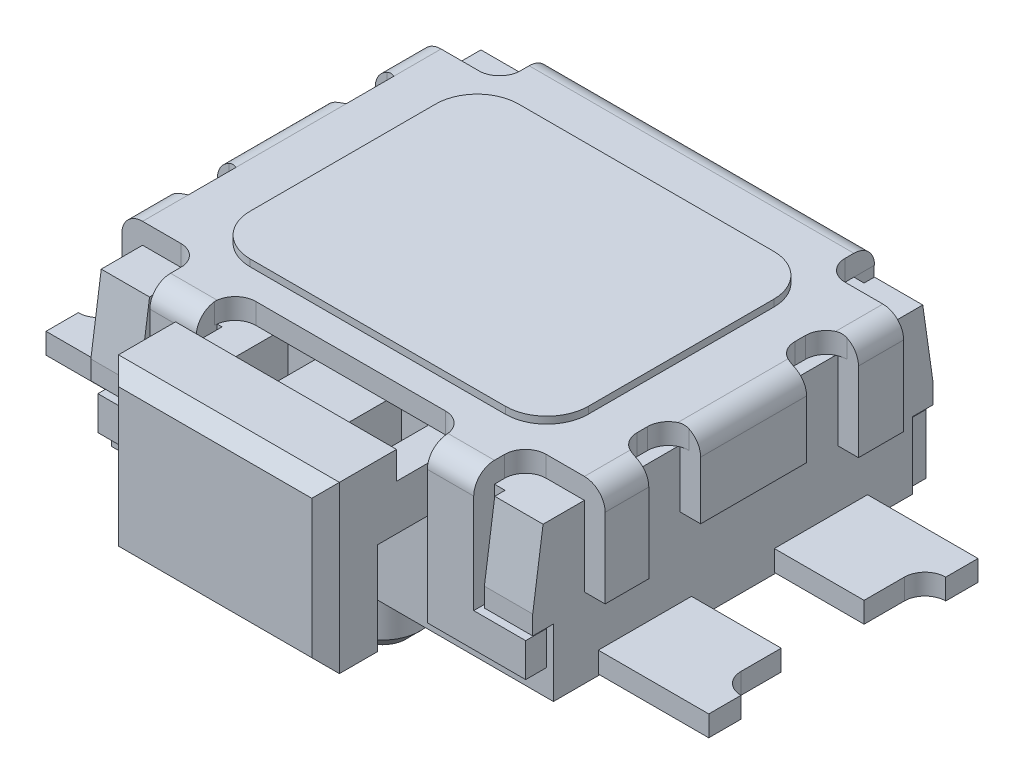
SolidWorks part; units mm, degrees
ref_plane "Front Plane" through (0, 0, 0) normal (0, 0, 1) x (1, 0, 0)
ref_plane "Top Plane" through (0, 0, 0) normal (0, 1, 0) x (1, 0, 0)
ref_plane "Right Plane" through (0, 0, 0) normal (1, 0, 0) x (0, 0, -1)
sketch "Sketch1" plane through (0, 0, 0) normal (0, 1, 0) x (1, 0, 0)
  line L1 (-1.75, 1.45) -> (1.75, 1.45)
  line L2 (-1.75, 1.45) -> (-1.75, -1.45)
  line L3 (-1.75, -1.45) -> (1.75, -1.45)
  line L4 (1.75, 1.45) -> (1.75, -1.45)
  line L5 (-1.75, 1.45) -> (1.75, -1.45) construction
  line L6 (-1.75, -1.45) -> (1.75, 1.45) construction
  point P0 (0, 0)
  dimension "D1" = 3.5
  dimension "D2" = 2.9
extrude "Boss-Extrude1" add sketch "Sketch1" along normal blind 1.3
fillet "Fillet1" radius 0.15 4 edges at (-1.75, 1.3, 0) (1.75, 1.3, 0) (0, 1.3, -1.45) (0, 1.3, 1.45)
sketch "Sketch2" plane through (0, 1.3, 0) normal (0, 1, 0) x (1, 0, 0)
  line L0 (4.873, 0.6414) -> (53.3412, 0.6414) construction
  line L1 (0, 1.45) -> (0, -1.3) construction
  line L2 (-1.75, 1.45) -> (-1.176, 1.45)
  line L3 (-1.75, 1.45) -> (-1.75, 1.0863)
  line L4 (-1.75, 1.0863) -> (-1.326, 1.0863)
  line L5 (-1.176, 1.45) -> (-1.176, 1.2363)
  line L6 (-1.75, 1.45) -> (1.75, 1.45) construction
  line L7 (-1.6, -1.3) -> (1.6, -1.3) construction
  line L8 (-1.75, -1.45) -> (-1.75, 1.45) construction
  line L9 (-1.75, -1.45) -> (-1.1728, -1.45)
  line L10 (-1.75, -1.45) -> (-1.75, -1.0755)
  line L11 (-1.75, -1.0755) -> (-1.3228, -1.0755)
  line L12 (-1.1728, -1.45) -> (-1.1728, -1.2255)
  line L13 (-1.75, 0.7594) -> (-1.6663, 0.7594)
  line L14 (-1.75, 0.7594) -> (-1.75, 0.3837)
  line L15 (-1.75, 0.3837) -> (-1.6663, 0.3837)
  line L16 (-1.5163, 0.6094) -> (-1.5163, 0.5337)
  line L17 (0, 0) -> (-1.75, 0) construction
  line L18 (-1.75, -0.3837) -> (-1.6663, -0.3837)
  line L19 (-1.5163, -0.6094) -> (-1.5163, -0.5337)
  line L20 (-1.75, -0.7594) -> (-1.6663, -0.7594)
  line L21 (-1.75, -0.7594) -> (-1.75, -0.3837)
  line L22 (1.75, -1.45) -> (-1.75, -1.45) construction
  line L23 (-0.8369, -1.45) -> (0.8369, -1.45)
  line L24 (-0.8369, -1.45) -> (-0.8369, -1.3181)
  line L25 (-0.6869, -1.1681) -> (0.6869, -1.1681)
  line L26 (0, -1.45) -> (0, -1.1681)
  line L27 (0.8369, -1.45) -> (0.8369, -1.3181)
  line L28 (1.75, -0.7594) -> (1.75, -0.3837)
  line L29 (1.75, -0.7594) -> (1.6663, -0.7594)
  line L30 (1.5163, -0.6094) -> (1.5163, -0.5337)
  line L31 (1.75, -0.3837) -> (1.6663, -0.3837)
  line L32 (1.75, 0.3837) -> (1.6663, 0.3837)
  line L33 (1.5163, 0.6094) -> (1.5163, 0.5337)
  line L34 (1.75, 0.7594) -> (1.6663, 0.7594)
  line L35 (1.75, 0.7594) -> (1.75, 0.3837)
  line L36 (1.75, 1.0863) -> (1.326, 1.0863)
  line L37 (1.176, 1.45) -> (1.176, 1.2363)
  line L38 (1.75, 1.45) -> (1.176, 1.45)
  line L39 (1.75, 1.45) -> (1.75, 1.0863)
  line L40 (1.75, -1.0755) -> (1.3228, -1.0755)
  line L41 (1.1728, -1.45) -> (1.1728, -1.2255)
  line L42 (1.75, -1.45) -> (1.1728, -1.45)
  line L43 (1.75, -1.45) -> (1.75, -1.0755)
  arc A0 (-1.3228, -1.0755) -> (-1.1728, -1.2255) centre (-1.3228, -1.2255) cw
  arc A1 (-1.326, 1.0863) -> (-1.176, 1.2363) centre (-1.326, 1.2363) ccw
  arc A2 (-1.6663, 0.3837) -> (-1.5163, 0.5337) centre (-1.6663, 0.5337) ccw
  arc A3 (-1.6663, 0.7594) -> (-1.5163, 0.6094) centre (-1.6663, 0.6094) cw
  arc A4 (-1.6663, -0.3837) -> (-1.5163, -0.5337) centre (-1.6663, -0.5337) cw
  arc A5 (-1.6663, -0.7594) -> (-1.5163, -0.6094) centre (-1.6663, -0.6094) ccw
  arc A6 (-0.8369, -1.3181) -> (-0.6869, -1.1681) centre (-0.6869, -1.3181) cw
  arc A7 (0.8369, -1.3181) -> (0.6869, -1.1681) centre (0.6869, -1.3181) ccw
  arc A8 (1.6663, -0.7594) -> (1.5163, -0.6094) centre (1.6663, -0.6094) cw
  arc A9 (1.6663, -0.3837) -> (1.5163, -0.5337) centre (1.6663, -0.5337) ccw
  arc A10 (1.6663, 0.3837) -> (1.5163, 0.5337) centre (1.6663, 0.5337) cw
  arc A11 (1.6663, 0.7594) -> (1.5163, 0.6094) centre (1.6663, 0.6094) ccw
  arc A12 (1.326, 1.0863) -> (1.176, 1.2363) centre (1.326, 1.2363) cw
  arc A13 (1.3228, -1.0755) -> (1.1728, -1.2255) centre (1.3228, -1.2255) ccw
  line M33 (1.6, -1.3) -> (1.6, 1.3)
  line M34 (1.6, 1.3) -> (-1.6, 1.3)
  line M35 (-1.6, 1.3) -> (-1.6, -1.3)
  line M36 (-1.6, -1.3) -> (1.6, -1.3)
  dimension "D1" = 0.15
  dimension "D2" = 0.15
  dimension "D3" = 0.15
extrude "Cut-Extrude1" cut sketch "Sketch2" against normal blind 0.15 contours L5 L2 L3 L4 M35 M34 | L20 A5 A4 L18 L21 M35 | A3 L13 L14 L15 A2 M35 | A0 L11 L12 M35 M36 | A6 L24 L23 L26 M36 | L27 A7 L26 L23 M36 | L31 A9 A8 L29 L28 M33 | L34 A11 A10 L32 L35 M33 | A12 L36 L37 M33 M34 | L39 L38 L37 L36 M34 M33 | A11 L33 A10 M33 | A9 L30 A8 M33 | A7 L25 L26 M36 | A6 L26 L25 M36 | L9 L12 L11 L10 M36 M35 | L4 A1 L5 M34 M35 | L42 L43 L40 L41 M33 M36 | L40 A13 L41 M36 M33 region at (-1.5205, 1.3, -1.3257) region at (-1.398, 1.3, -1.1973) region at (1.398, 1.3, -1.1973) region at (1.5205, 1.3, -1.3257) region at (-1.6757, 1.3, -0.5715) region at (-1.6757, 1.3, 0.5715) region at (1.5635, 1.3, -0.5715) region at (1.6757, 1.3, -0.5715) region at (-1.5212, 1.3, 1.3226) region at (-1.396, 1.3, 1.1919) region at (1.5635, 1.3, 0.5715) region at (1.6757, 1.3, 0.5715) region at (1.396, 1.3, 1.1919) region at (1.5212, 1.3, 1.3226) region at (-0.4184, 1.3, 1.375) region at (-0.4008, 1.3, 1.2356) region at (0.4184, 1.3, 1.375) region at (0.4008, 1.3, 1.2356)
sketch "Sketch3" plane through (-1.75, 0, 0) normal (-1, 0, 0) x (0, 0, 1)
  line L0 (-1.45, 0) -> (1.45, 0) construction
  line L1 (-0.7594, 1.15) -> (-0.3837, 1.15)
  line L2 (-0.7594, 1.15) -> (-0.7594, 0)
  line L3 (-0.7594, 0) -> (-0.3837, 0)
  line L4 (-0.3837, 1.15) -> (-0.3837, 0.7316)
  line L5 (-0.3837, 0.7316) -> (-0.3837, 0) construction
  line L6 (0.3837, 1.15) -> (0.7594, 1.15)
  line L7 (0.3837, 1.15) -> (0.3837, 0.7316)
  line L8 (0.3837, 0) -> (0.7594, 0)
  line L9 (0.7594, 1.15) -> (0.7594, 0)
  line L10 (1.0755, 1.15) -> (1.45, 1.15)
  line L11 (1.0755, 1.15) -> (1.0755, 0)
  line L12 (1.0755, 0) -> (1.45, 0)
  line L13 (1.45, 1.15) -> (1.45, 0)
  line L14 (-1.0863, 1.15) -> (-1.45, 1.15)
  line L15 (-1.0863, 1.15) -> (-1.0863, 0)
  line L16 (-1.0863, 0) -> (-1.45, 0)
  line L17 (-1.45, 1.15) -> (-1.45, 0)
  line L18 (-0.3837, 0) -> (0.3837, 0)
  line L19 (-0.3837, 0) -> (-0.3837, 0.7316) construction
  line L20 (-0.3837, 0.7316) -> (0.3837, 0.7316)
  line L21 (0.3837, 0) -> (0.3837, 0.7316) construction
  line L22 (0.3837, 0.7316) -> (0.3837, 0) construction
extrude "Cut-Extrude2" cut sketch "Sketch3" against normal blind 0.15
mirror "Mirror1" about plane through (0, 0, 0) normal (1, 0, 0) of "Cut-Extrude2"
sketch "Sketch5" plane through (0, 0, 1.45) normal (0, 0, 1) x (1, 0, 0)
  line L0 (-1.6, 0) -> (1.6, 0) construction
  line L1 (-0.8369, 1.15) -> (0.8369, 1.15)
  line L2 (-0.8369, 1.15) -> (-0.8369, 0.1872)
  line L3 (-0.8369, 0) -> (0.8369, 0)
  line L4 (0.8369, 1.15) -> (0.8369, 0.1872)
  line L5 (-1.6, 1.15) -> (-1.6, 0) construction
  line L6 (1.1728, 1.15) -> (1.6, 1.15)
  line L7 (1.1728, 1.15) -> (1.1728, 0.4318)
  line L8 (1.1728, 0.4318) -> (1.6, 0.4318)
  line L9 (1.6, 1.15) -> (1.6, 0.4318)
  line L10 (-1.1728, 1.15) -> (-1.6, 1.15)
  line L11 (-1.1728, 1.15) -> (-1.1728, 0.4318)
  line L12 (-1.1728, 0.4318) -> (-1.6, 0.4318)
  line L13 (-1.6, 1.15) -> (-1.6, 0.4318)
  line L14 (0, 0) -> (0, 1.15) construction
  line L15 (-1.6, 0) -> (-0.8369, 0)
  line L16 (-1.6, 0) -> (-1.6, 0.1872)
  line L17 (-1.6, 0.1872) -> (-0.8369, 0.1872)
  line L18 (-0.8369, 0) -> (-0.8369, 0.1872) construction
  line L19 (1.6, 0.1872) -> (0.8369, 0.1872)
  line L20 (0.8369, 0) -> (0.8369, 0.1872) construction
  line L21 (1.6, 0) -> (0.8369, 0)
  line L22 (1.6, 0) -> (1.6, 0.1872)
  line L23 (-0.8369, 0.1872) -> (-0.8369, 0) construction
  line L24 (0.8369, 0.1872) -> (0.8369, 0) construction
extrude "Cut-Extrude3" cut sketch "Sketch5" against normal blind 0.15
sketch "Sketch8" plane through (0, 0, -1.45) normal (0, 0, -1) x (-1, 0, 0)
  line L1 (-0.8369, 0) -> (0.8369, 0)
  line L2 (-0.8369, 0) -> (-0.8369, 0.418)
  line L3 (-0.8369, 0.418) -> (0.8369, 0.418)
  line L4 (-1.1728, 1.15) -> (-1.6, 1.15)
  line L5 (-1.6, 1.15) -> (-1.6, 0.4318)
  line L6 (-1.6, 0.4318) -> (-1.1728, 0.4318)
  line L7 (-1.1728, 0.4318) -> (-1.1728, 1.15)
  line L8 (-1.1728, 1.15) -> (-1.6, 1.15)
  line L9 (-1.6, 1.15) -> (-1.6, 0.4318)
  line L10 (-1.6, 0.4318) -> (-1.1728, 0.4318)
  line L11 (-1.1728, 0.4318) -> (-1.1728, 1.15)
  line L12 (0.8369, 1.15) -> (-0.8369, 1.15)
  line L13 (-0.8369, 1.15) -> (-0.8369, 0.1872)
  line L14 (-0.8369, 0) -> (0.8369, 0)
  line L15 (0.8369, 0.1872) -> (0.8369, 1.15)
  line L16 (0.8369, 1.15) -> (-0.8369, 1.15) construction
  line L17 (-0.8369, 1.15) -> (-0.8369, 0.1872) construction
  line L18 (-0.8369, 0) -> (0.8369, 0) construction
  line L19 (0.8369, 0.1872) -> (0.8369, 1.15) construction
  line L20 (1.6, 1.15) -> (1.1728, 1.15)
  line L21 (1.1728, 1.15) -> (1.1728, 0.4318)
  line L22 (1.1728, 0.4318) -> (1.6, 0.4318)
  line L23 (1.6, 0.4318) -> (1.6, 1.15)
  line L24 (1.6, 1.15) -> (1.1728, 1.15)
  line L25 (1.1728, 1.15) -> (1.1728, 0.4318)
  line L26 (1.1728, 0.4318) -> (1.6, 0.4318)
  line L27 (1.6, 0.4318) -> (1.6, 1.15)
  line L28 (0.8369, 0) -> (0.8369, 0.418)
  line L38 (-0.8369, 0.1872) -> (-1.6, 0.1872)
  line L40 (-1.6, 0.1872) -> (-1.6, 0)
  line L42 (-1.6, 0) -> (-0.8369, 0)
  line L44 (0.8369, 0) -> (1.6, 0)
  line L46 (1.6, 0) -> (1.6, 0.1872)
  line L48 (1.6, 0.1872) -> (0.8369, 0.1872)
  point P14 (0.8369, 0.0371)
  dimension "D1" = 0
  dimension "D2" = 0
  dimension "D3" = 0
extrude "Cut-Extrude5" cut sketch "Sketch8" against normal blind 0.15
sketch "Sketch9" plane through (0, 0, 1.45) normal (0, 0, 1) x (1, 0, 0)
  line L0 (-1.6, 0) -> (-0.8369, 0) construction
  line L1 (-1.6, 0.4318) -> (-1.5491, 0.4318)
  line L2 (-1.6, 0.4318) -> (-1.6, 0)
  line L3 (-1.6, 0) -> (-1.5491, 0)
  line L4 (-1.5491, 0.4318) -> (-1.5491, 0)
  line L5 (0, 0) -> (0, 1.3) construction
  line L6 (-0.6869, 1.3) -> (0.6869, 1.3) construction
  line L7 (1.6, 0) -> (1.5491, 0)
  line L8 (1.5491, 0.4318) -> (1.5491, 0)
  line L9 (1.6, 0.4318) -> (1.5491, 0.4318)
  line L10 (1.6, 0.4318) -> (1.6, 0)
extrude "Cut-Extrude6" cut sketch "Sketch9" against normal blind 0.15
mirror "Mirror2" about plane through (0, 0, 0) normal (0, 0, 1) of "Cut-Extrude6"
sketch "Sketch10" plane through (-1.6, 0, 0) normal (-1, 0, 0) x (0, 0, 1)
  line L0 (-1.3, 1.15) -> (-1.375, 1.15)
  line L1 (-1.45, 1.15) -> (-1.3, 1.15) construction
  line L2 (-1.375, 1.15) -> (-1.45, 0.6241)
  line L3 (-1.45, 1.15) -> (-1.45, 0.4318) construction
  line L4 (-1.45, 0.6241) -> (-1.45, 0.4866)
  line L5 (-1.45, 0.4866) -> (-1.3, 0.4866)
  line L6 (-1.3, 0) -> (-1.3, 1.15) construction
  line L7 (-1.3, 0.4866) -> (-1.3, 1.15)
  line L8 (0, 0) -> (0, 1.3) construction
  line L9 (-0.3991, 1.3) -> (0.3991, 1.3) construction
  line L10 (1.45, 0.4866) -> (1.3, 0.4866)
  line L11 (1.45, 0.6241) -> (1.45, 0.4866)
  line L12 (1.375, 1.15) -> (1.45, 0.6241)
  line L13 (1.3, 1.15) -> (1.375, 1.15)
  line L14 (1.3, 0.4866) -> (1.3, 1.15)
extrude "Boss-Extrude2" add sketch "Sketch10" against normal blind 0.35
mirror "Mirror3" about plane through (0, 0, 0) normal (1, 0, 0) of "Boss-Extrude2"
sketch "Sketch11" plane through (-1.75, 0, 0) normal (-1, 0, 0) x (0, 0, 1)
  line L0 (1.0755, 1.15) -> (1.0755, 0) construction
  line L1 (-1.0863, 0) -> (1.0755, 0)
  line L2 (-1.0863, 0) -> (-1.0863, 0.575)
  line L3 (-1.0863, 0.575) -> (1.0755, 0.575)
  line L4 (1.0755, 0) -> (1.0755, 0.575)
extrude "Cut-Extrude7" cut sketch "Sketch11" against normal blind 0.15
mirror "Mirror4" about plane through (0, 0, 0) normal (1, 0, 0) of "Cut-Extrude7"
sketch "Sketch12" plane through (0, 1.3, 0) normal (0, 1, 0) x (1, 0, 0)
  line L1 (-0.9241, 0.9718) -> (0.9241, 0.9718)
  line L2 (-1.2241, 0.6718) -> (-1.2241, -0.6718)
  line L3 (-0.9241, -0.9718) -> (0.9241, -0.9718)
  line L4 (1.2241, 0.6718) -> (1.2241, -0.6718)
  line L5 (-1.2241, 0.9718) -> (1.2241, -0.9718) construction
  line L6 (-1.2241, -0.9718) -> (1.2241, 0.9718) construction
  arc A0 (0.9241, -0.9718) -> (1.2241, -0.6718) centre (0.9241, -0.6718) ccw
  arc A1 (0.9241, 0.9718) -> (1.2241, 0.6718) centre (0.9241, 0.6718) cw
  arc A2 (-1.2241, -0.6718) -> (-0.9241, -0.9718) centre (-0.9241, -0.6718) ccw
  arc A3 (-0.9241, 0.9718) -> (-1.2241, 0.6718) centre (-0.9241, 0.6718) ccw
  point P0 (0, 0)
  point P6 (1.2241, -0.9718)
  dimension "D1" = 0.3
extrude "Boss-Extrude3" add sketch "Sketch12" along normal blind 0.05
sketch "Sketch13" plane through (0, 0, 0) normal (1, 0, 0) x (0, 0, -1)
  line L0 (-1.3, 1.15) -> (-1.6367, 1.15)
  line L1 (-1.3, 1.15) -> (-1.3, 0.1872) construction
  line L2 (-1.6367, 1.15) -> (-1.6367, 1.35)
  line L3 (-1.6367, 1.35) -> (-2.15, 1.35)
  line L4 (-2.15, 1.35) -> (-2.15, 0.15)
  line L5 (-2.15, 0.15) -> (-1.7736, 0.15)
  line L6 (-1.7736, 0.15) -> (-1.7736, 0.8202)
  line L7 (-1.7736, 0.8202) -> (-1.3, 0.8202)
  line L8 (-1.3, 0.8202) -> (-1.3, 1.15)
  line L9 (1.45, 1.15) -> (1.45, 0.4318) construction
  line L10 (0.9718, 1.35) -> (-0.9718, 1.35) construction
  point P16 (-1.3, 1.213)
  dimension "D1" = 3.6
  dimension "D2" = 1.2
extrude "Boss-Extrude4" add sketch "Sketch13" along normal mid plane 1.6
sketch "Sketch14" plane through (0, 1.15, 0) normal (0, 1, 0) x (1, 0, 0)
  line L0 (-0.3768, -1.6367) -> (-0.5635, -1.45)
  line L1 (0.8, -1.6367) -> (-0.8, -1.6367) construction
  line L2 (-0.8369, -1.45) -> (0.8369, -1.45) construction
  line L3 (-0.5635, -1.45) -> (-0.5635, -1.1681)
  line L4 (-0.6869, -1.1681) -> (0.6869, -1.1681) construction
  line L5 (-0.5635, -1.1681) -> (-0.5635, -1.0597)
  line L6 (-0.5635, -1.0597) -> (-0.2578, -1.0597)
  line L7 (-0.2578, -1.0597) -> (-0.2578, -1.6367)
  line L8 (0.8, -1.6367) -> (-0.8, -1.6367) construction
  line L9 (-0.2578, -1.6367) -> (-0.3768, -1.6367)
  line L10 (0, 0) -> (0, -2.15) construction
  line L11 (0.8, -2.15) -> (-0.8, -2.15) construction
  line L12 (0.2578, -1.0597) -> (0.2578, -1.6367)
  line L13 (0.5635, -1.0597) -> (0.2578, -1.0597)
  line L14 (0.5635, -1.1681) -> (0.5635, -1.0597)
  line L15 (0.5635, -1.45) -> (0.5635, -1.1681)
  line L16 (0.3768, -1.6367) -> (0.5635, -1.45)
  line L17 (0.2578, -1.6367) -> (0.3768, -1.6367)
extrude "Cut-Extrude8" cut sketch "Sketch14" against normal up to surface (0.3298 mm away) up to face at (0, 0.8202, 1.5368)
chamfer "Chamfer1" distance 0.1 angle 45 4 edges at (0, 1.35, 2.15) (0.8, 0.75, 2.15) (0, 0.15, 2.15) (-0.8, 0.75, 2.15)
sketch "Sketch15" plane through (1.6, 0, 0) normal (1, 0, 0) x (0, 0, -1)
  line L0 (0, 0) -> (0, 1.35) construction
  line L1 (-0.975, 0.01) -> (-0.3, 0.01)
  line L2 (-0.975, 0.01) -> (-0.975, 0.16)
  line L3 (-0.975, 0.16) -> (-0.3, 0.16)
  line L4 (-0.3, 0.01) -> (-0.3, 0.16)
  line L5 (1.3, 0) -> (-1.3, 0) construction
  line L6 (-0.6718, 1.35) -> (0.6718, 1.35) construction
  line L7 (0.975, 0.16) -> (0.3, 0.16)
  line L8 (0.3, 0.01) -> (0.3, 0.16)
  line L9 (0.975, 0.01) -> (0.3, 0.01)
  line L10 (0.975, 0.01) -> (0.975, 0.16)
  dimension "D1" = 0.15
  dimension "D2" = 0.6
  dimension "D3" = 1.95
  dimension "D4" = 0.01
extrude "Boss-Extrude5" add sketch "Sketch15" along normal blind 0.8
mirror "Mirror5" about plane through (0, 0, 0) normal (1, 0, 0) of "Boss-Extrude5"
sketch "Sketch16" plane through (2.4, 0, 0) normal (1, 0, 0) x (0, 0, -1)
  line L0 (-0.3, 0.16) -> (-0.975, 0.16) construction
  line L1 (-0.3, 0.01) -> (-0.7414, 0.01)
  line L2 (-0.3, 0.01) -> (-0.3, 0.16)
  line L3 (-0.3, 0.16) -> (-0.7414, 0.16)
  line L4 (-0.7414, 0.01) -> (-0.7414, 0.16)
  line L5 (0, 0) -> (0, 1.35) construction
  line L6 (1.3, 0) -> (-1.3, 0) construction
  line L7 (-0.6718, 1.35) -> (0.6718, 1.35) construction
  line L8 (0.3, 0.16) -> (0.7414, 0.16)
  line L9 (0.7414, 0.01) -> (0.7414, 0.16)
  line L10 (0.3, 0.01) -> (0.7414, 0.01)
  line L11 (0.3, 0.01) -> (0.3, 0.16)
extrude "Cut-Extrude9" cut sketch "Sketch16" against normal blind 0.15
mirror "Mirror6" about plane through (0, 0, 0) normal (1, 0, 0) of "Cut-Extrude9"
fillet "Fillet2" radius 0.15 4 edges at (2.25, 0.085, -0.7414) (2.25, 0.085, 0.7414) (-2.25, 0.085, 0.7414) (-2.25, 0.085, -0.7414)
sketch "Sketch17" plane through (0, 0, 0) normal (0, -1, 0) x (1, 0, 0)
  line L0 (0, 1.3) -> (0, -1.3) construction
  line L1 (0.2578, 1.3) -> (-0.2578, 1.3) construction
  line L2 (0.8369, -1.3) -> (-0.8369, -1.3) construction
  line L3 (-1.6, 0) -> (1.6, 0) construction
  line L4 (-1.6, 0.3837) -> (-1.6, -0.3837) construction
  line L5 (1.6, -1.3) -> (1.6, 1.3) construction
  circle A0 centre (0, 0.94) radius 0.275
  circle A1 centre (0, -0.94) radius 0.275
  dimension "D1" = 0.55
  dimension "D2" = 1.88
extrude "Boss-Extrude6" add sketch "Sketch17" along normal blind 0.5
chamfer "Chamfer2" distance 0.1 angle 45 2 edges at (0, -0.5, -1.215) (0, -0.5, 0.665)
